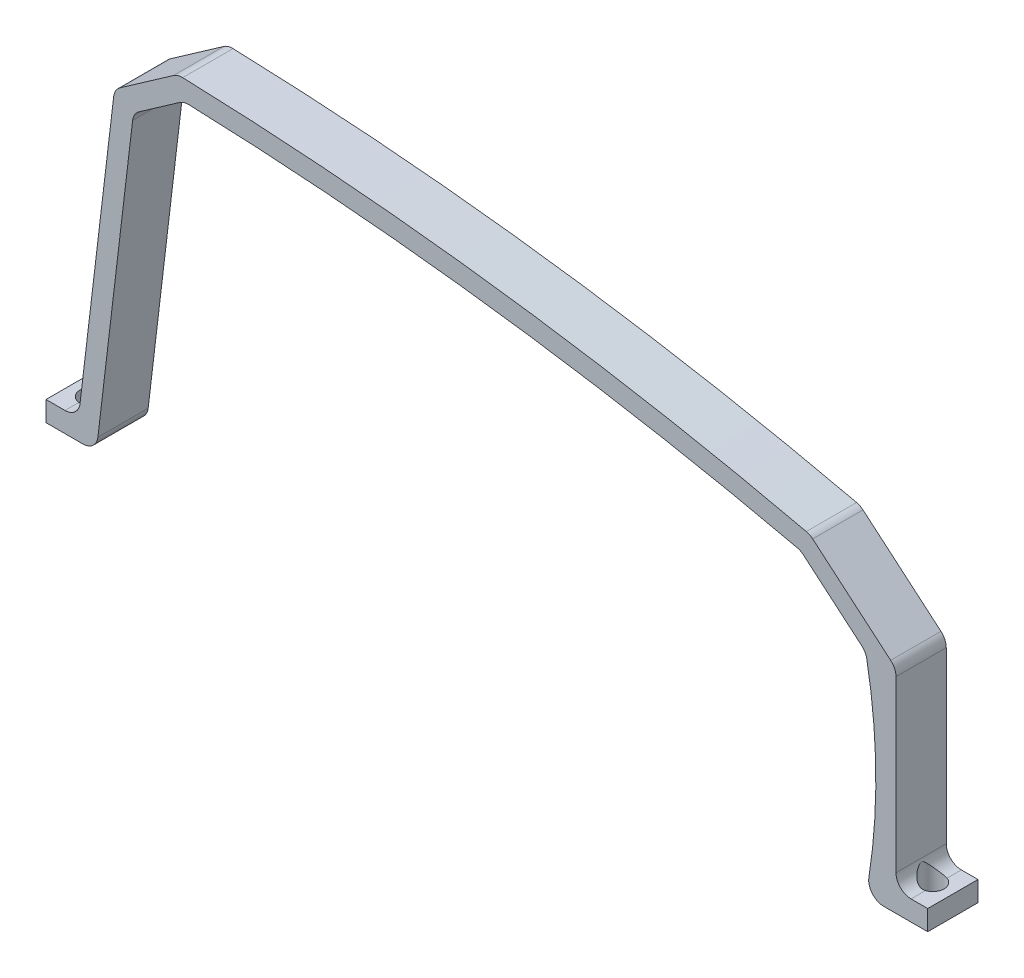
SolidWorks part; units mm, degrees
ref_plane "Plan de face" through (0, 0, 0) normal (0, 0, 1) x (1, 0, 0)
ref_plane "Plan de dessus" through (0, 0, 0) normal (0, 1, 0) x (1, 0, 0)
ref_plane "Plan de droite" through (0, 0, 0) normal (1, 0, 0) x (0, 0, -1)
sketch "Esquisse1" plane through (0, 0, 0) normal (0, 0, 1) x (1, 0, 0)
  line L0 (0, 0) -> (7.381, 62)
  line L1 (7.381, 62) -> (17.381, 69)
  line L2 (17.381, 69) -> (140.0385, 53) construction
  line L3 (140.0385, 53) -> (153, 42)
  line L4 (153, 42) -> (153, 0) construction
  line L5 (153, 42) -> (5, 42) construction
  line L6 (7.381, 62) -> (7.381, 0) construction
  line L7 (0, 0) -> (153, 0) construction
  line L8 (17.381, 69) -> (17.381, 0) construction
  line L9 (140.0385, 53) -> (140.0385, 0) construction
  line L19 (78.7097, 61) -> (79.0978, 63.9748) construction
  line L20 (155, 21) -> (153, 21) construction
  line L21 (-3.972, 0.4729) -> (3.6206, 64.2504)
  line L22 (3.6206, 64.2504) -> (16.1775, 73.0402)
  line L23 (141.8864, 56.6781) -> (156.6516, 44.1473)
  line L24 (-3.972, 0.4729) -> (-3.972, 0)
  line L25 (-3.972, 0) -> (0, 0)
  line L26 (153, 0) -> (159, 0)
  line L27 (159, 0) -> (159, 42.1543)
  line L28 (159, 42.1543) -> (156.6516, 44.1473)
  line L29 (155, 21) -> (159, 21) construction
  arc A0 (17.381, 69) -> (140.0385, 53) centre (-3.5607, -569.6934) cw
  arc A1 (153, 42) -> (153, 0) centre (43.75, 21) cw
  arc A2 (16.1775, 73.0402) -> (141.8864, 56.6781) centre (-3.5607, -569.6934) cw
  arc A4 (156.6516, 44.1473) -> (156.9281, -0.7551) centre (43.75, 21) cw construction
  dimension "D1" = 62
  dimension "D2" = 153
  dimension "D3" = 42
  dimension "D4" = 17
  dimension "D5" = 148
  dimension "D6" = 69
  dimension "D7" = 53
  dimension "D8" = 10
  dimension "D9" = 3
  dimension "D10" = 2
  dimension "D12" = 4
  dimension "D11" = 4
extrude "Boss.-Extru.1" add sketch "Esquisse1" along normal blind 10
sketch "Esquisse2" plane through (0, 0, 10) normal (0, 0, 1) x (1, 0, 0)
  line L0 (0, 0) -> (0, 4)
  line L1 (0, 4) -> (-10, 4)
  line L2 (-10, 4) -> (-10, 0)
  line L3 (-10, 0) -> (0, 0)
  line L4 (155.3094, 4) -> (153, 0)
  line L5 (153, 0) -> (165.3094, 0)
  line L7 (155.3094, 4) -> (165.3094, 4)
  line L8 (165.3094, 0) -> (165.3094, 4)
  dimension "D1" = 4
  dimension "D2" = 10
  dimension "D3" = 60
extrude "Boss.-Extru.2" add sketch "Esquisse2" against normal up to vertex (10 mm away) up to point (-3.972, 0.4729, 0)
sketch "Esquisse3" plane through (0, 4, 0) normal (0, 1, 0) x (1, 0, 0)
  line L0 (-10, -5) -> (-3.5521, -5) construction
  line L1 (-10, 0) -> (-10, -10) construction
  line L3 (159, -5) -> (165.3094, -5) construction
  line L5 (165.3094, 0) -> (165.3094, -10) construction
  line L6 (-3.5521, 0) -> (-3.5521, -10) construction
  line L7 (159, -10) -> (159, 0) construction
  circle A0 centre (-6, -5) radius 2.25
  circle A1 centre (161.3094, -5) radius 2.25
  point P4 (-6, -5)
  point P8 (160.4201, -5)
  dimension "D1" = 4.5
  dimension "D2" = 4
  dimension "D3" = 4
extrude "Enlèv. mat.-Extru.1" cut sketch "Esquisse3" against normal through all both and the other way through all
fillet "Congé1" radius 3 12 edges at (7.381, 62, 5) (16.1775, 73.0402, 5) (3.6206, 64.2504, 5) (153, 42, 5) (140.0385, 53, 5) (141.8864, 56.6781, 5) (159, 42.1543, 5) (159, 4, 5) (153, 0, 5) (17.381, 69, 5) (0, 0, 5) (-3.5521, 4, 5)
